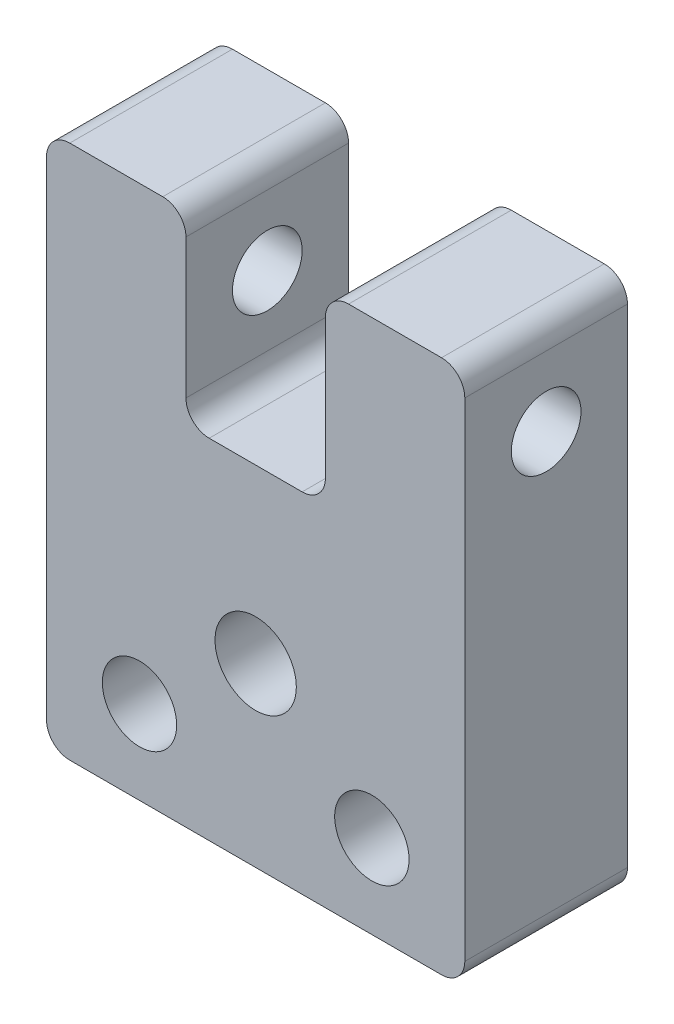
SolidWorks part; units mm, degrees
ref_plane "Alzado" through (0, 0, 0) normal (0, 0, 1) x (1, 0, 0)
ref_plane "Planta" through (0, 0, 0) normal (0, 1, 0) x (1, 0, 0)
ref_plane "Vista lateral" through (0, 0, 0) normal (1, 0, 0) x (0, 0, -1)
sketch "Croquis1" plane through (0, 0, 0) normal (0, 0, 1) x (1, 0, 0)
  line L0 (3, 11.5) -> (9, 11.5)
  line L1 (-9, 11.5) -> (-3, 11.5)
  line L2 (-9, 11.5) -> (-9, -11.5)
  line L3 (-9, -11.5) -> (9, -11.5)
  line L4 (9, 11.5) -> (9, -11.5)
  line L5 (-9, 11.5) -> (9, -11.5) construction
  line L6 (-9, -11.5) -> (9, 11.5) construction
  line L7 (-3, 11.5) -> (3, 11.5) construction
  line L8 (-3, 11.5) -> (-3, 3.5)
  line L9 (-3, 3.5) -> (3, 3.5)
  line L10 (3, 11.5) -> (3, 3.5)
  line L11 (0, 0) -> (0, -11.5) construction
  circle A1 centre (5, -7.9) radius 1.6
  circle A2 centre (-5, -7.9) radius 1.6
  circle A3 centre (0, -3.9) radius 1.75
  point P0 (0, 0)
  point P10 (0, 3.5)
  point P19 (5, -9.5)
  dimension "D5" = 4
  dimension "D7" = 3.2
  dimension "D6" = 3.5
  dimension "D1" = 18
  dimension "D2" = 23
  dimension "D3" = 6
  dimension "D4" = 8
  dimension "D8" = 10
  dimension "D9" = 2
extrude "Saliente-Extruir1" add sketch "Croquis1" along normal mid plane 7
sketch "Croquis2" plane through (0, 0, 0) normal (1, 0, 0) x (0, 0, -1)
  line L0 (-3.5, 11.5) -> (3.5, 11.5) construction
  circle A0 centre (0, 7.5) radius 1.5
  dimension "D1" = 3
  dimension "D2" = 4
extrude "Cortar-Extruir1" cut sketch "Croquis2" against normal through all both and the other way through all
fillet "Redondeo1" radius 1 8 edges at (9, -11.5, 0) (-9, -11.5, 0) (-9, 11.5, 0) (-3, 11.5, 0) (-3, 3.5, 0) (3, 3.5, 0) (3, 11.5, 0) (9, 11.5, 0)
